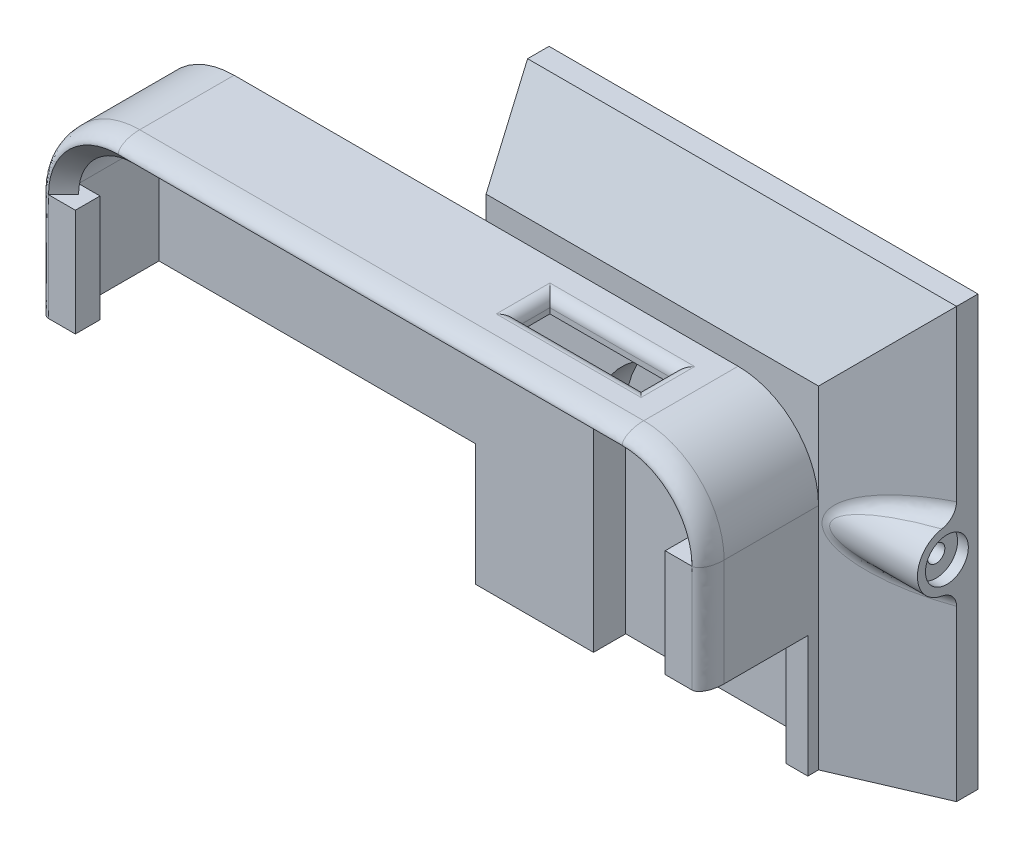
SolidWorks part; units mm, degrees
ref_plane "Front Plane" through (0, 0, 0) normal (0, 0, 1) x (1, 0, 0)
ref_plane "Top Plane" through (0, 0, 0) normal (0, 1, 0) x (1, 0, 0)
ref_plane "Right Plane" through (0, 0, 0) normal (1, 0, 0) x (0, 0, -1)
sketch "Sketch1" plane through (0, 0, 0) normal (0, 0, 1) x (1, 0, 0)
  line L0 (31, 17.5) -> (31, 0)
  line L1 (0, 0) -> (62, 0)
  line L2 (0, 0) -> (0, 10)
  line L3 (7.5, 17.5) -> (54.5, 17.5)
  line L4 (62, 0) -> (62, 10)
  line L5 (7.5, 16) -> (54.5, 16)
  line L9 (1.5, 0) -> (1.5, 10)
  line L12 (60.5, 10) -> (60.5, 0)
  arc A0 (0, 10) -> (7.5, 17.5) centre (7.5, 10) cw
  arc A1 (62, 10) -> (54.5, 17.5) centre (54.5, 10) ccw
  arc A2 (1.5, 10) -> (7.5, 16) centre (7.5, 10) cw
  arc A3 (60.5, 10) -> (54.5, 16) centre (54.5, 10) ccw
  dimension "D5" = 1.5
extrude "Boss-Extrude1" add sketch "Sketch1" along normal blind 10.8 contours L9 A2 L5 L0 L3 A0 L2 L1 | A3 L12 L1 L4 A1 L3 L0 L5 region at (42.75, 17.144, 0) region at (30.644, 16.75, 0)
sketch "Sketch2" plane through (0, 0, 0) normal (0, 0, -1) x (-1, 0, 0)
  line L0 (-1.5, 0) -> (-1.5, 10)
  line L1 (-7.5, 16) -> (-54.5, 16)
  line L2 (-60.5, 0) -> (-60.5, 10)
  line L3 (-60.5, 0) -> (-1.5, 0)
  arc A0 (-1.5, 10) -> (-7.5, 16) centre (-7.5, 10) ccw
  arc A1 (-54.5, 16) -> (-60.5, 10) centre (-54.5, 10) ccw
extrude "Boss-Extrude2" add sketch "Sketch2" against normal blind 1 separate body
combine bodies "Combine1" operation type add bodies to combine 102 101
sketch "Sketch3" plane through (0, 0, 10.8) normal (0, 0, 1) x (1, 0, 0)
  line L0 (0, 0) -> (3.5, 0)
  line L1 (0, 0) -> (0, 10)
  line L2 (0, 0) -> (0, 10) construction
  line L3 (3.5, 0) -> (3.5, 10)
  line L4 (3.5, 10) -> (0, 10)
  line L5 (1.5, 10) -> (1.5, 0)
  line L6 (31, 16) -> (31, -7.5027)
  line L7 (7.5, 16) -> (54.5, 16) construction
  line L8 (60.5, 10) -> (60.5, 0)
  line L9 (62, 0) -> (58.5, 0)
  line L10 (58.5, 10) -> (62, 10)
  line L11 (58.5, 0) -> (58.5, 10)
  line M7 (1.5, 0) -> (1.5, 10)
  line M11 (60.5, 10) -> (60.5, 0)
  dimension "D1" = 3.5
  dimension "D2" = 10
extrude "Boss-Extrude3" add sketch "Sketch3" against normal blind 2.3 contours L3 L4 L0 M7 | L11 L9 L10 M11 region at (2.5, 5, 10.8) region at (59.5, 5, 10.8)
fillet "Fillet1" radius 1 5 edges at (0, 5, 10.8) (62, 5, 10.8) (2.1967, 15.3033, 10.8) (59.8033, 15.3033, 10.8) (31, 17.5, 10.8) second distance 2 first distance on face at (31, 9.4708, 10.8)
sketch "Sketch4" plane through (0, 17.5, 0) normal (0, 1, 0) x (1, 0, 0)
  line L0 (62, -8.8) -> (62, 0) construction
  line L1 (51.5, -6.05) -> (40, -6.05)
  line L2 (51.5, -6.05) -> (51.5, -3.05)
  line L3 (51.5, -3.05) -> (40, -3.05)
  line L4 (40, -6.05) -> (40, -3.05)
  line L5 (7.5, 0) -> (54.5, 0) construction
  dimension "D1" = 10.5
  dimension "D2" = 11.5
  dimension "D3" = 3.05
  dimension "D4" = 3
extrude "Cut-Extrude1" cut sketch "Sketch4" against normal up to next
sketch "Sketch5" plane through (0, 0, 10.8) normal (0, 0, 1) x (1, 0, 0)
  line L1 (7.5, 15) -> (54.5, 15)
  line L2 (7.5, 16) -> (54.5, 16) construction
  line L4 (3.5, 10) -> (1.5, 10) construction
  line L5 (31, 16.5) -> (31, -2.3238) construction
  line L6 (54.5, 16.5) -> (7.5, 16.5) construction
  line L7 (59.5, 10) -> (60.5, 10)
  line L8 (54.5, 16) -> (7.5, 16)
  line L9 (1.5, 10) -> (2.5, 10)
  arc A1 (2.5, 10) -> (7.5, 15) centre (7.5, 10) cw
  arc A2 (59.5, 10) -> (54.5, 15) centre (54.5, 10) ccw
  arc A3 (60.5, 10) -> (54.5, 16) centre (54.5, 10) ccw
  arc A4 (7.5, 16) -> (1.5, 10) centre (7.5, 10) ccw
  dimension "D1" = 1
extrude "Boss-Extrude4" add sketch "Sketch5" against normal blind 2.3
chamfer "Chamfer1" distance 1.5 angle 45 3 edges at (58.0355, 13.5355, 10.8) (31, 15, 10.8) (3.9645, 13.5355, 10.8)
chamfer "Chamfer3" distance 1 angle 45 3 edges at (58.0355, 13.5355, 8.5) (31, 15, 8.5) (3.9645, 13.5355, 8.5)
sketch "Sketch6" plane through (0, 0, 0) normal (0, 0, -1) x (-1, 0, 0)
  line L0 (-59.98, 0) -> (-59.98, 6.7)
  line L1 (-59.98, 0) -> (-42.02, 0)
  line L2 (-42.02, 0) -> (-42.02, 6.7)
  arc A0 (-42.02, 6.7) -> (-59.98, 6.7) centre (-51, 6.7) ccw
extrude "Cut-Extrude2" cut sketch "Sketch6" against normal blind 2
sketch "Sketch9" plane through (0, 0, 0) normal (0, 0, -1) x (-1, 0, 0)
  line L0 (-62, 10) -> (-62, 0)
  line L1 (-62, 0) -> (-59.98, 0)
  line L2 (-59.98, 0) -> (-59.98, 6.7)
  line L3 (-42.02, 6.7) -> (-42.02, 0)
  line L4 (-42.02, 0) -> (-40, 0)
  line L5 (-42.02, 0) -> (0, 0) construction
  line L6 (-40, 0) -> (-40, 10)
  line L8 (-54.5, 17.5) -> (-47.5, 17.5)
  arc A0 (-59.98, 6.7) -> (-42.02, 6.7) centre (-51, 6.7) cw
  arc A1 (-47.5, 17.5) -> (-40, 10) centre (-47.5, 10) cw
  arc A2 (-54.5, 17.5) -> (-62, 10) centre (-54.5, 10) ccw
extrude "Boss-Extrude6" add sketch "Sketch9" along normal blind 2
fillet "Fillet2" radius 1 4 edges at (45.75, 17.5, 3.05) (51.5, 17.5, 4.55) (45.75, 17.5, 6.05) (40, 17.5, 4.55)
sketch "Sketch10" plane through (0, 0, -2) normal (0, 0, -1) x (-1, 0, 0)
  line L0 (-62, 10) -> (-62, 0)
  line L1 (-62, 0) -> (-40, 0)
  line L2 (-40, 0) -> (-40, 10)
  line L3 (-54.5, 17.5) -> (-47.5, 17.5)
  arc A0 (-62, 10) -> (-54.5, 17.5) centre (-54.5, 10) cw
  arc A1 (-40, 10) -> (-47.5, 17.5) centre (-47.5, 10) ccw
extrude "Boss-Extrude7" add sketch "Sketch10" along normal blind 1.87
sketch "Sketch11" plane through (0, 0, -2) normal (0, 0, 1) x (1, 0, 0)
  circle A0 centre (51, 8.65) radius 2.5
  dimension "D1" = 5
extrude "Cut-Extrude3" cut sketch "Sketch11" against normal through all
sketch "Sketch20" plane through (0, 0, -3.87) normal (0, 0, -1) x (-1, 0, 0)
  line L0 (-51, 28.65) -> (-51, -11.35) construction
  line L1 (-71, 28.65) -> (-31, 28.65)
  line L2 (-71, 28.65) -> (-71, -11.35)
  line L3 (-71, -11.35) -> (-31, -11.35)
  line L4 (-31, 28.65) -> (-31, -11.35)
  line L5 (-71, 8.65) -> (-31, 8.65) construction
  line L7 (-68.6, 26.25) -> (-33.4, 26.25)
  line L8 (-68.6, 26.25) -> (-68.6, -8.95)
  line L9 (-68.6, -8.95) -> (-33.4, -8.95)
  line L10 (-33.4, 26.25) -> (-33.4, -8.95)
  circle A0 centre (-51, 8.65) radius 2.5 construction
  dimension "D1" = 40
  dimension "D2" = 40
  dimension "D3" = 0
  dimension "D4" = 0
  dimension "D5" = 35.2
  dimension "D6" = 35.2
  dimension "D7" = 17.6
  dimension "D8" = 17.6
extrude "Boss-Extrude8" add sketch "Sketch20" along normal blind 2 separate body
sketch "Sketch21" plane through (0, 0, 0) normal (0, -1, 0) x (1, 0, 0)
  line L0 (62, -3.87) -> (71, -3.87)
  line L1 (71, -3.87) -> (62, 0)
  line L2 (62, 8.8) -> (62, -3.87) construction
  line L3 (62, 0) -> (62, -3.87)
  dimension "D1" = 9
extrude "Boss-Extrude9" add sketch "Sketch21" along normal up to surface and the other way up to surface up to face at (51, -11.35, -4.87) other way up to face at (51, 28.65, -4.87)
sketch "Sketch28" plane through (0, 0, 0) normal (0, 0, -1) x (-1, 0, 0)
  line L0 (-31, 17.5) -> (-31, 0)
  line L1 (-31, -11.35) -> (-31, 28.65) construction
  line L4 (-40, 10) -> (-40, 0)
  line L5 (-40, 0) -> (0, 0)
  line L6 (0, 0) -> (0, 10)
  line L7 (-7.5, 17.5) -> (-47.5, 17.5)
  line L8 (-40, 10) -> (-40, 0)
  line L9 (-40, 0) -> (0, 0)
  line L10 (0, 0) -> (0, 10)
  line L11 (-7.5, 17.5) -> (-47.5, 17.5)
  arc A2 (-40, 10) -> (-47.5, 17.5) centre (-47.5, 10) ccw
  arc A3 (0, 10) -> (-7.5, 17.5) centre (-7.5, 10) ccw
  arc A4 (-40, 10) -> (-47.5, 17.5) centre (-47.5, 10) ccw
  arc A5 (0, 10) -> (-7.5, 17.5) centre (-7.5, 10) ccw
  arc M7 (-47.5, 17.5) -> (-40, 10) centre (-47.5, 10) cw
  line M8 (-40, 10) -> (-40, 0)
  line M9 (-40, 0) -> (0, 0)
  line M12 (-7.5, 17.5) -> (-47.5, 17.5)
  dimension "D1" = 0
extrude "Boss-Extrude22" add sketch "Sketch28" along normal up to surface (3.87 mm away) contours L0 M12 M7 M8 M9 region at (35.9396, 9.2536, 0) up to face at (53.5, 8.65, -3.87)
sketch "Sketch29" plane through (31, 0, 0) normal (-1, 0, 0) x (0, 0, 1)
  line L0 (-3.87, 28.65) -> (-3.87, 19.65)
  line L1 (-3.87, 17.5) -> (-3.87, 28.65) construction
  line L2 (-3.87, 19.65) -> (0, 19.65)
  line L3 (0, 19.65) -> (-3.87, 28.65)
  line L4 (-3.87, 28.65) -> (-3.8304, 28.713)
  line M6 (-3.87, 17.5) -> (-3.87, 28.65)
  dimension "D1" = 9
extrude "Boss-Extrude23" add sketch "Sketch29" against normal up to surface (40 mm away) contours L2 L3 M6 region at (31, 22.65, -2.58) up to face at (71, 8.65, -4.87)
sketch "Sketch30" plane through (0, 19.65, 0) normal (0, -1, 0) x (1, 0, 0)
  line L3 (62, 0) -> (71, -3.87)
  line L4 (71, -3.87) -> (71, 0)
  line L5 (71, 0) -> (62, 0)
  line L6 (62, 0) -> (71, -3.87)
  line L7 (71, -3.87) -> (71, 0)
  line L8 (71, 0) -> (62, 0)
  dimension "D1" = 0
extrude "Cut-Extrude8" cut sketch "Sketch30" against normal up to next
sketch "Sketch31" plane through (62, 0, 0) normal (-1, 0, 0) x (0, 0, 1)
  line L3 (0, 28.65) -> (-3.87, 28.65)
  line L4 (-3.87, 28.65) -> (0, 19.65)
  line L5 (0, 19.65) -> (0, 28.65)
  line L6 (0, 28.65) -> (-3.87, 28.65)
  line L7 (-3.87, 28.65) -> (0, 19.65)
  line L8 (0, 19.65) -> (0, 28.65)
  dimension "D1" = 0
extrude "Cut-Extrude9" cut sketch "Sketch31" against normal up to next
sketch "Sketch32" plane through (0, 19.65, 0) normal (0, -1, 0) x (1, 0, 0)
  line L5 (62, -3.87) -> (62, 0)
  line L6 (62, 0) -> (31, 0)
  line L7 (31, 0) -> (31, -3.87)
  line L8 (31, -3.87) -> (33.4, -3.87)
  line L9 (33.4, -3.87) -> (62, -3.87)
  line L10 (62, -3.87) -> (62, 0)
  line L11 (62, 0) -> (31, 0)
  line L12 (31, 0) -> (31, -3.87)
  line L13 (31, -3.87) -> (33.4, -3.87)
  line L14 (33.4, -3.87) -> (62, -3.87)
  dimension "D1" = 0
extrude "Boss-Extrude24" add sketch "Sketch32" along normal up to surface (2.15 mm away) up to face at (45.75, 17.5, 4.55)
sketch "Sketch33" plane through (0, 0, -3.87) normal (0, 0, -1) x (-1, 0, 0)
  line L0 (-54.5, 17.5) -> (-62, 17.5)
  line L1 (-62, 17.5) -> (-62, 10)
  arc A0 (-62, 10) -> (-54.5, 17.5) centre (-54.5, 10) cw
extrude "Boss-Extrude25" add sketch "Sketch33" against normal up to surface (3.87 mm away) up to face at (48.1, 18.36, 0)
sketch "Sketch34" plane through (0, 0, 0) normal (0, -1, 0) x (1, 0, 0)
  line L0 (60.5, 1) -> (62, 1)
  line L1 (31, 0) -> (31, 1)
  line L20 (0, 0) -> (31, 0)
  line L21 (31, 0) -> (31, -3.87)
  line L22 (31, -3.87) -> (33.4, -3.87)
  line L23 (33.4, -3.87) -> (62, -3.87)
  line L24 (62, -3.87) -> (62, 0)
  line L25 (62, 0) -> (62, 8.8)
  line L26 (61, 10.8) -> (58.5, 10.8)
  line L27 (58.5, 10.8) -> (58.5, 8.5)
  line L28 (58.5, 8.5) -> (60.5, 8.5)
  line L29 (60.5, 8.5) -> (60.5, 1)
  line L30 (60.5, 1) -> (59.98, 1)
  line L31 (59.98, 1) -> (59.98, -2)
  line L32 (59.98, -2) -> (42.02, -2)
  line L33 (42.02, -2) -> (42.02, 1)
  line L34 (42.02, 1) -> (1.5, 1)
  line L35 (1.5, 1) -> (1.5, 8.5)
  line L36 (1.5, 8.5) -> (3.5, 8.5)
  line L37 (3.5, 8.5) -> (3.5, 10.8)
  line L38 (3.5, 10.8) -> (1, 10.8)
  line L39 (0, 8.8) -> (0, 0)
  line L40 (0, 0) -> (31, 0)
  line L41 (31, 0) -> (31, -3.87)
  line L42 (31, -3.87) -> (33.4, -3.87)
  line L43 (33.4, -3.87) -> (62, -3.87)
  line L44 (62, -3.87) -> (62, 0)
  line L45 (62, 0) -> (62, 8.8)
  line L46 (61, 10.8) -> (58.5, 10.8)
  line L47 (58.5, 10.8) -> (58.5, 8.5)
  line L48 (58.5, 8.5) -> (60.5, 8.5)
  line L49 (60.5, 8.5) -> (60.5, 1)
  line L50 (60.5, 1) -> (59.98, 1)
  line L51 (59.98, 1) -> (59.98, -2)
  line L52 (59.98, -2) -> (42.02, -2)
  line L53 (42.02, -2) -> (42.02, 1)
  line L54 (42.02, 1) -> (1.5, 1)
  line L55 (1.5, 1) -> (1.5, 8.5)
  line L56 (1.5, 8.5) -> (3.5, 8.5)
  line L57 (3.5, 8.5) -> (3.5, 10.8)
  line L58 (3.5, 10.8) -> (1, 10.8)
  line L59 (0, 8.8) -> (0, 0)
  spline S2 degree 2 poles (-2769.6454, -979.1152) (73.4069, -63.5955) (61.954, 9.3993) (61.9047, 9.714) (61.807, 9.9811) (61.6887, 10.3047) (61.5165, 10.5125) (61.4097, 10.6416) (61.2894, 10.7144) (34.7566, 26.7839) (-231.209, -2974.6133) knots -62.059776 -62.059776 -62.059776 0.25 0.25 0.5 0.5 0.75 0.75 0.875 0.875 24.347049 24.347049 24.347049 only from (62, 8.8) to (61, 10.8)
  spline S3 degree 2 poles (259.0787, -2977.8645) (27.3521, 26.7647) (0.7111, 10.7147) (0.592, 10.643) (0.4846, 10.5139) (0.3135, 10.3082) (0.1946, 9.9856) (0.0962, 9.7183) (0.0462, 9.4006) (-11.3863, -63.1555) (2809.0718, -1041.6058) knots -23.400529 -23.400529 -23.400529 0.125 0.125 0.25 0.25 0.5 0.5 0.75 0.75 62.676656 62.676656 62.676656 only from (1, 10.8) to (0, 8.8)
  spline S4 degree 2 poles (62, 8.8) (62, 9.1064) (61.954, 9.3993) (61.9047, 9.714) (61.807, 9.9811) (61.6887, 10.3047) (61.5165, 10.5125) (61.4097, 10.6416) (61.2894, 10.7144) (61.1481, 10.8) (61, 10.8) knots 0 0 0 0.25 0.25 0.5 0.5 0.75 0.75 0.875 0.875 1 1 1
  spline S5 degree 2 poles (1, 10.8) (0.8527, 10.8) (0.7111, 10.7147) (0.592, 10.643) (0.4846, 10.5139) (0.3135, 10.3082) (0.1946, 9.9856) (0.0962, 9.7183) (0.0462, 9.4006) (0, 9.1077) (0, 8.8) knots 0 0 0 0.125 0.125 0.25 0.25 0.5 0.5 0.75 0.75 1 1 1
  line M24 (31, 0) -> (31, -3.87)
  line M25 (31, -3.87) -> (33.4, -3.87)
  line M26 (33.4, -3.87) -> (62, -3.87)
  line M27 (62, -3.87) -> (62, 0)
  line M28 (62, 0) -> (62, 8.8)
  line M34 (60.5, 1) -> (59.98, 1)
  line M35 (59.98, 1) -> (59.98, -2)
  line M36 (59.98, -2) -> (42.02, -2)
  line M37 (42.02, -2) -> (42.02, 1)
  line M38 (42.02, 1) -> (1.5, 1)
  dimension "D1" = 0
extrude "Boss-Extrude26" add sketch "Sketch34" along normal up to surface (11.35 mm away) contours L1 L0 M24 M25 M26 M27 M28 M34 M35 M36 M37 M38 region at (58.1075, 0, -2.3535) region at (39.3369, 0, -1.8217) up to face at (57.25, -11.35, -4.2142)
sketch "Sketch37" plane through (71, 0, 0) normal (1, 0, 0) x (0, 0, -1)
  line L1 (3.87, -11.35) -> (3.87, 28.65) construction
  circle A0 centre (2.97, 8.65) radius 0.8065
  dimension "D2" = 1.613
  dimension "D3" = 0.9
  dimension "D1" = 17.6
extrude "Cut-Extrude13" cut sketch "Sketch37" against normal up to surface (17.5 mm away) up to face at (53.5, 8.65, -2)
sketch "Sketch38" plane through (71, 0, 0) normal (1, 0, 0) x (0, 0, -1)
  line L0 (3.87, 11.2486) -> (3.87, 6.0514)
  line L1 (3.87, -11.35) -> (3.87, 28.65) construction
  circle A0 centre (2.97, 8.65) radius 2.75
  line M3 (3.87, 28.65) -> (3.87, -11.35)
  dimension "D1" = 5.5
extrude "Boss-Extrude27" add sketch "Sketch38" against normal up to surface (9 mm away) contours A0 M3 region at (71, 8.65, -2.2712) up to face at (62, 0.3833, 4.65)
sketch "Sketch39" plane through (71, 0, 0) normal (1, 0, 0) x (0, 0, -1)
  circle A0 centre (2.97, 8.65) radius 2
  dimension "D1" = 4
extrude "Cut-Extrude15" cut sketch "Sketch39" against normal blind 1
sketch "Sketch40" plane through (70, 0, 0) normal (1, 0, 0) x (0, 0, -1)
  circle A0 centre (2.97, 8.65) radius 0.8065
  dimension "D1" = 1.613
extrude "Cut-Extrude16" cut sketch "Sketch40" against normal up to surface (21.5 mm away) up to face at (53.4961, 8.79, -2.1757)
fillet "Fillet3" radius 1.5 1 edges at (62.5116, 8.65, -0.22)
